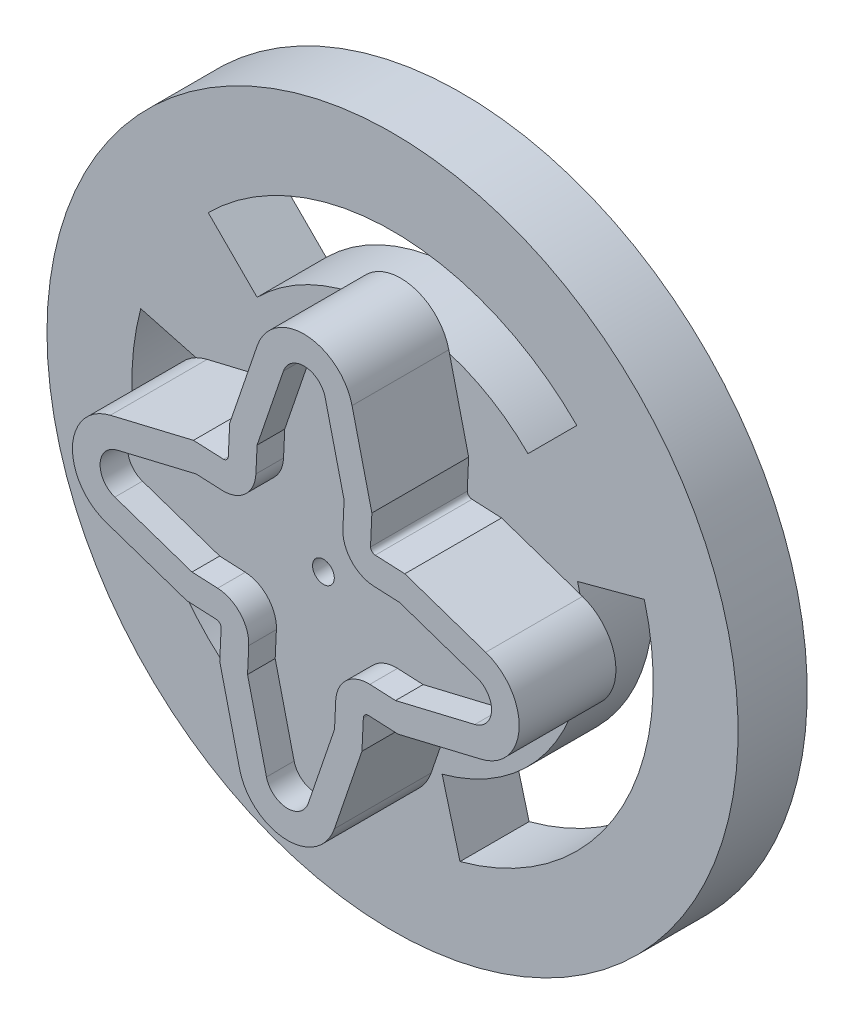
SolidWorks part; units mm, degrees
note: The reader was unsure of these and kept them because the rebuilt part matched: shared geometry of "Sketch1<5>", "Sketch1<6>".
ref_plane "Front Plane" through (0, 0, 0) normal (0, 0, 1) x (1, 0, 0)
ref_plane "Top Plane" through (0, 0, 0) normal (0, 1, 0) x (1, 0, 0)
ref_plane "Right Plane" through (0, 0, 0) normal (1, 0, 0) x (0, 0, -1)
sketch "Sketch1" plane through (0, 0, 0) normal (0, 0, 1) x (1, 0, 0)
  line L0 (-9.1568, 4.4766) -> (-6.6609, 4.3626)
  line L1 (-3.6642, 7.2217) -> (-3.5535, 9.5768)
  line L2 (-3.5535, 9.5768) -> (-1.1393, 16.6685)
  line L3 (2.6994, 16.488) -> (4.4377, 9.2011)
  line L4 (4.4377, 9.2011) -> (4.3237, 6.7052)
  line L5 (7.1828, 3.7085) -> (9.5379, 3.5978)
  line L6 (9.5379, 3.5978) -> (16.6296, 1.1836)
  line L7 (16.4491, -2.6551) -> (9.1622, -4.3934)
  line L8 (9.1622, -4.3934) -> (6.8071, -4.2827)
  line L9 (3.6696, -7.1385) -> (3.5589, -9.4935)
  line L10 (3.5589, -9.4935) -> (1.1447, -16.5853)
  line L11 (-4.4323, -9.1179) -> (-2.694, -16.4048)
  line L12 (-4.4323, -9.1179) -> (-4.3216, -6.7628)
  line L13 (-7.1774, -3.6253) -> (-9.5325, -3.5146)
  line L14 (-9.5325, -3.5146) -> (-16.6242, -1.1004)
  line L15 (-16.4437, 2.7383) -> (-9.1568, 4.4766)
  line L16 (0.8479, 18.0218) -> (-0.8425, -17.9385) construction
  line L17 (-17.9774, 0.8868) -> (17.9828, -0.8036) construction
  circle A0 centre (0, 0) radius 25.4
  arc A1 (-6.6609, 4.3626) -> (-3.6642, 7.2217) centre (-6.6609, 7.3626) ccw
  arc A2 (-1.1393, 16.6685) -> (2.6994, 16.488) centre (0.754, 16.024) cw
  arc A3 (4.3237, 6.7052) -> (7.1828, 3.7085) centre (7.3237, 6.7052) ccw
  arc A4 (16.6296, 1.1836) -> (16.4491, -2.6551) centre (15.985, -0.7097) cw
  arc A5 (6.8071, -4.2827) -> (3.6696, -7.1385) centre (6.6663, -7.2794) ccw
  arc A6 (1.1447, -16.5853) -> (-2.694, -16.4048) centre (-0.7486, -15.9407) cw
  arc A7 (-4.3216, -6.7628) -> (-7.1774, -3.6253) centre (-7.3183, -6.622) ccw
  arc A8 (-16.6242, -1.1004) -> (-16.4437, 2.7383) centre (-15.9797, 0.7929) cw
extrude "Extrude-Thin1" add sketch "Sketch1" along normal blind 2.54 thin contours A8 L14 L13 A7 L12 L11 A6 L10 L9 A5 L8 L7 A4 L6 L5 A3 L4 L3 A2 L2 L1 A1 L0 L15
extrude "Extrude-Thin2" add sketch "Sketch1<5>" against normal blind 6.35 thin contours A8 L14 L13 A7 L12 L11 A6 L10 L9 A5 L8 L7 A4 L6 L5 A3 L4 L3 A2 L2 L1 A1 L0 L15 thin type one direction wall 2.54
sketch "Sketch1<5>" plane through (0, 0, 0) normal (0, 0, 1) x (1, 0, 0) same geometry as "Sketch1"
extrude "Boss-Extrude1" add sketch "Sketch1<6>" against normal blind 6.35 contours A8 L14 L13 A7 L12 L11 A6 L10 L9 A5 L8 L7 A4 L6 L5 A3 L4 L3 A2 L2 L1 A1 L0 L15
sketch "Sketch1<6>" plane through (0, 0, 0) normal (0, 0, 1) x (1, 0, 0) same geometry as "Sketch1"
sketch "Sketch2" plane through (0, 0, -6.35) normal (0, 0, -1) x (-1, 0, 0)
  circle A0 centre (0, 0) radius 31.75
  dimension "D1" = 63.5
extrude "Boss-Extrude2" add sketch "Sketch2" along normal blind 6.35
sketch "Sketch3" plane through (0, 0, -12.7) normal (0, 0, -1) x (-1, 0, 0)
  line L0 (0, 0) -> (16.9343, 16.9343) construction
  line L1 (0, 0) -> (0, 16.3795) construction
  line L2 (0, 0) -> (-16.9343, 16.9343) construction
  line L3 (-16.9343, 16.9343) -> (-12.4442, 12.4442)
  line L4 (16.9343, 16.9343) -> (12.4442, 12.4442)
  line L5 (6.1984, -23.1327) -> (4.5549, -16.999)
  line L6 (23.1327, 6.1984) -> (16.999, 4.5549)
  line L7 (-23.1327, 6.1984) -> (-16.999, 4.5549)
  line L8 (-6.1984, -23.1327) -> (-4.5549, -16.999)
  arc A0 (16.9343, 16.9343) -> (-16.9343, 16.9343) centre (0, 0) ccw
  arc A1 (-12.4442, 12.4442) -> (12.4442, 12.4442) centre (0, 0) cw
  arc A2 (16.999, 4.5549) -> (4.5549, -16.999) centre (0, 0) cw
  arc A3 (6.1984, -23.1327) -> (23.1327, 6.1984) centre (0, 0) ccw
  arc A4 (-4.5549, -16.999) -> (-16.999, 4.5549) centre (0, 0) cw
  arc A5 (-23.1327, 6.1984) -> (-6.1984, -23.1327) centre (0, 0) ccw
  point P17 (0, 0)
  dimension "D1" = 90
  dimension "D2" = 6.35
extrude "Cut-Extrude1" cut sketch "Sketch3" against normal blind 6.35
sketch "Sketch4" plane through (0, 0, -12.7) normal (0, 0, -1) x (-1, 0, 0)
  circle A0 centre (0, 0) radius 1
  dimension "D1" = 2
extrude "Cut-Extrude2" cut sketch "Sketch4" against normal through all
chamfer "Chamfer2" distance 2.54 angle 45 1 edges at (-1, 0, -12.7)
